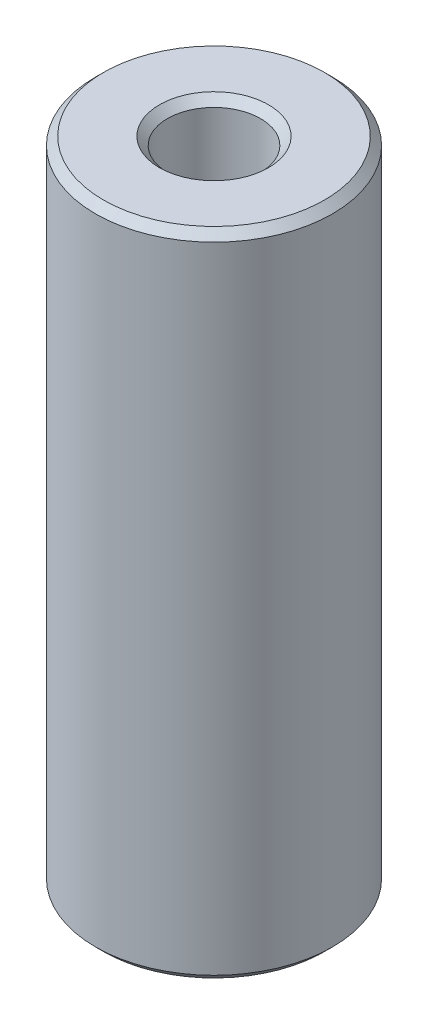
SolidWorks part; units mm, degrees
ref_plane "Front Plane" through (0, 0, 0) normal (0, 0, 1) x (1, 0, 0)
ref_plane "Top Plane" through (0, 0, 0) normal (0, 1, 0) x (1, 0, 0)
ref_plane "Right Plane" through (0, 0, 0) normal (1, 0, 0) x (0, 0, -1)
sketch "Sketch1" plane through (0, 0, 0) normal (0, 1, 0) x (1, 0, 0)
  circle A0 centre (0, 0) radius 50
  dimension "SLEEVE_OD" = 100
extrude "Boss-Extrude1" add sketch "Sketch1" along normal blind 274.5986
sketch "Sketch2" plane through (0, 0, 0) normal (0, 1, 0) x (1, 0, 0)
  circle A0 centre (0, 0) radius 19.6478
  dimension "BORE_D" = 39.2956
extrude "Cut-Extrude1" cut sketch "Sketch2" along normal through all
chamfer "Chamfer1" distance 3.3641 angle 45 4 edges at (0, 274.5986, 19.6478) (0, 0, 19.6478) (0, 0, 50) (0, 274.5986, 50)
